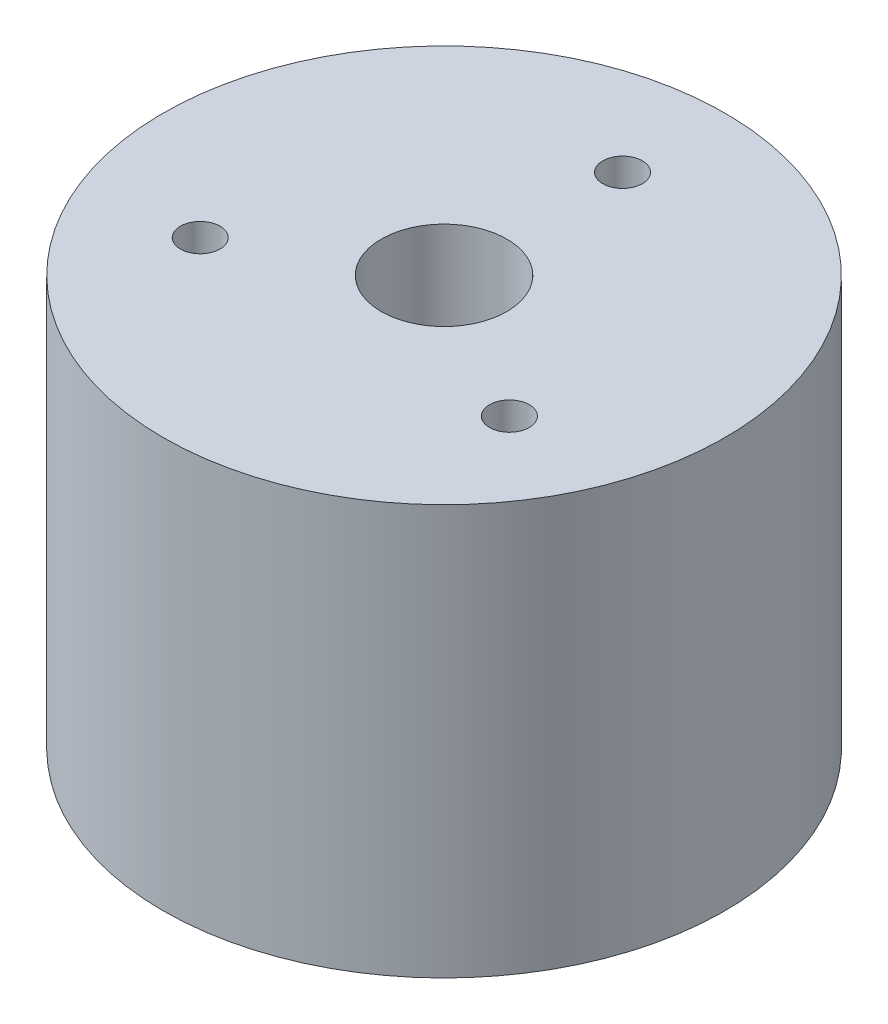
SolidWorks part; units mm, degrees
ref_plane "前视基准面" through (0, 0, 0) normal (0, 0, 1) x (1, 0, 0)
ref_plane "上视基准面" through (0, 0, 0) normal (0, 1, 0) x (1, 0, 0)
ref_plane "右视基准面" through (0, 0, 0) normal (1, 0, 0) x (0, 0, -1)
sketch "草图1" plane through (0, 0, 0) normal (0, 1, 0) x (1, 0, 0)
  line L0 (0, 34.1091) -> (0, -33.6188) construction
  line L1 (0, 0) -> (24.6958, 14.2581) construction
  circle A0 centre (0, 0) radius 21.25
  circle A1 centre (0, 0) radius 13.5 construction
  circle A2 centre (0, 0) radius 12.15 construction
  circle A3 centre (0, 0) radius 4.75
  circle A4 centre (0, 13.5) radius 1.5
  circle A5 centre (11.6913, -6.75) radius 1.5
  circle A6 centre (-11.6913, -6.75) radius 1.5
  circle A7 centre (10.5222, 6.075) radius 1.5
  circle A8 centre (0, -12.15) radius 1.5
  circle A9 centre (-10.5222, 6.075) radius 1.5
  point P14 (0, 0)
  point P25 (0, 0)
  dimension "D1" = 42.5
  dimension "D2" = 27
  dimension "D3" = 24.3
  dimension "D4" = 9.5
  dimension "D5" = 3
  dimension "D6" = 3
  dimension "D7" = 3
  dimension "D8" = 3
extrude "凸台-拉伸1" add sketch "草图1" along normal blind 31 contours A0 A9 A8 A7 A6 A5 A4 A3 | A8 | A9 | A7 region at (-20.649, 0, 0)
extrude "切除-拉伸1" cut sketch "草图1<3>" along normal blind 5 contours A7 | A9 | A8
sketch "草图1<3>" plane through (0, 0, 0) normal (0, 1, 0) x (1, 0, 0) same geometry as "草图1"
